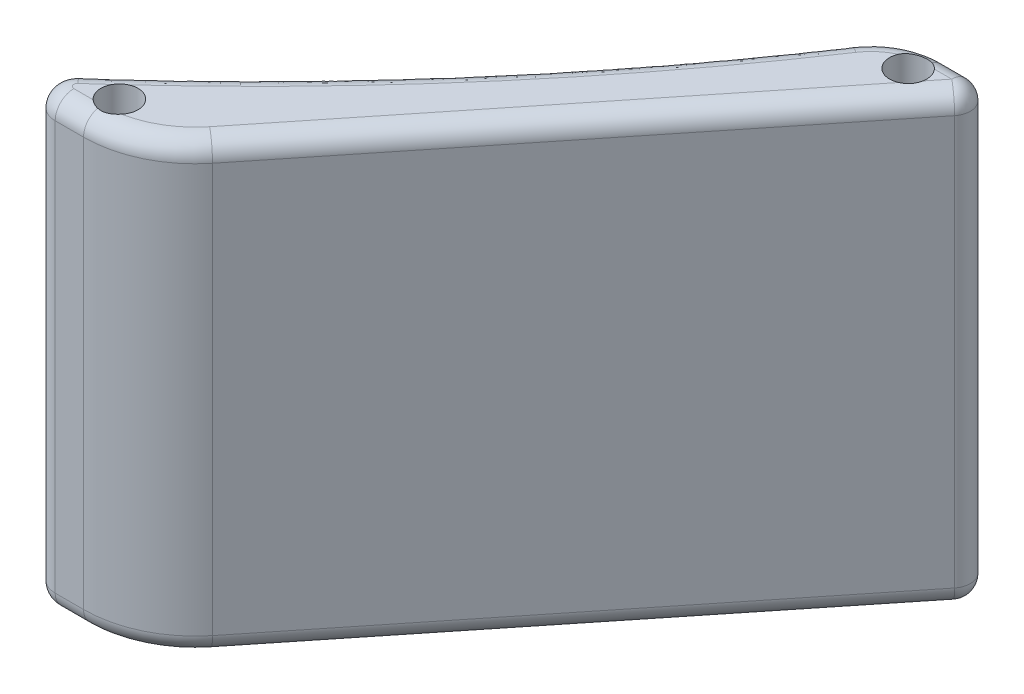
SolidWorks part; units mm, degrees
ref_plane "Front Plane" through (0, 0, 0) normal (0, 0, 1) x (1, 0, 0)
ref_plane "Top Plane" through (0, 0, 0) normal (0, 1, 0) x (1, 0, 0)
ref_plane "Right Plane" through (0, 0, 0) normal (1, 0, 0) x (0, 0, -1)
sketch "Sketch1" plane through (0, 0, 0) normal (0, 0, 1) x (1, 0, 0)
  line L1 (0, 0) -> (-4, 0)
  line L2 (0, 0) -> (0, 12)
  line L3 (0, 12) -> (-4, 12)
  line L4 (-4, 0) -> (-4, 12)
  dimension "D1" = 12
  dimension "D2" = 4
ref_plane "Plane1" through (0, 0, 10) normal (0, 0, 1) x (1, 0, 0)
sketch3d "3DSketch2"
  line L0 (-4, 12, 0) -> (-14.4203, 12, 13.0254)
  dimension "D1" = 16.6806
sweep "Sweep1" add profiles "Sketch1" path "3DSketch2"
sketch "Sketch6" plane through (0, 12, 0) normal (0, 1, 0) x (1, 0, 0)
  line L1 (-2.154, 1.0025) -> (-6.7019, 0.5258)
  line L2 (-6.7019, 0.5258) -> (-14.8517, -8.4683)
  line L3 (-14.8517, -8.4683) -> (-15.1128, -13.7534)
  spline S0 degree 2 poles (-2.154, 1.0025) (-7.3815, -7.4825) (-15.1128, -13.7534) knots 0 0 0 1 1 1
extrude "Cut-Extrude1" cut sketch "Sketch6" against normal through all contours L3 S0 L1 L2
fillet "Fillet6" radius 0.6 1 edges at (-14.2324, 6, 13.0254)
fillet "Fillet7" radius 3 1 edges at (-10.4203, 6, 13.0254)
fillet "Fillet8" radius 2 1 edges at (-2.7854, 6, 0)
fillet "Fillet9" radius 0.5 1 edges at (0, 6, 0)
sketch "Sketch7" plane through (0, 12, 0) normal (0, 1, 0) x (1, 0, 0)
  circle A0 centre (-1.8768, -0.8354) radius 0.5
  circle A1 centre (-11.7669, -12.1555) radius 0.5
  dimension "D1" = 1
  dimension "D2" = 1
extrude "Cut-Extrude2" cut sketch "Sketch7" against normal through all
fillet "Fillet10" radius 0.5 16 edges at (-0.5897, 12, 0.2834) (-1.3731, 12, 0) (-2.648, 12, 0.2358) (-13.1847, 12, 12.6389) (-12.2431, 12, 13.0254) (-10.5626, 12, 12.7293) (-0.5897, 0, 0.2834) (-1.3731, 0, 0) (-2.648, 0, 0.2358) (-13.1847, 0, 12.6389) (-12.2431, 0, 13.0254) (-10.5626, 0, 12.7293) (-5.0847, 12, 6.3559) (-5.0847, 0, 6.3559)
